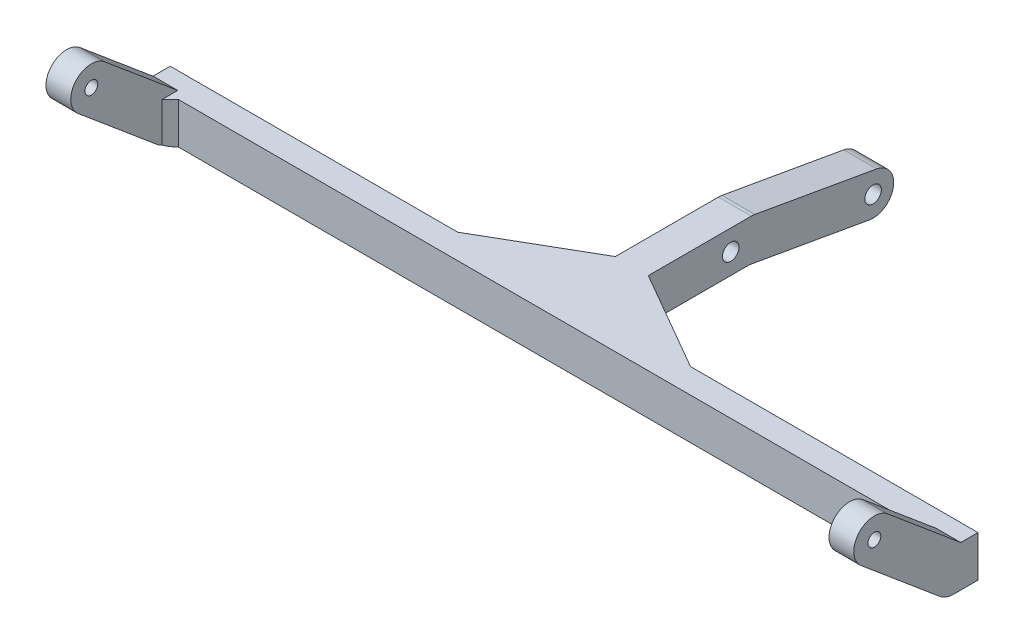
SolidWorks part; units mm, degrees
material "1060 合金"
ref_plane "前视基准面" through (0, 0, 0) normal (0, 0, 1) x (1, 0, 0)
ref_plane "上视基准面" through (0, 0, 0) normal (0, 1, 0) x (1, 0, 0)
ref_plane "右视基准面" through (0, 0, 0) normal (1, 0, 0) x (0, 0, -1)
sketch "草图1" plane through (0, 0, 0) normal (0, 1, 0) x (1, 0, 0)
  line L0 (0, 105.6524) -> (0, -42.1429) construction
  line L1 (98, 0) -> (-98, 0)
  line L7 (-24.7846, 8) -> (-4, 20)
  line L10 (-98, 8) -> (-24.7846, 8)
  line L20 (4, 50) -> (-4, 50)
  line L24 (-4, 20) -> (-4, 50)
  line L25 (-98, 0) -> (-98, 8)
  line L28 (98, 0) -> (98, 8)
  line L29 (4, 20) -> (4, 50)
  line L32 (98, 8) -> (24.7846, 8)
  line L33 (24.7846, 8) -> (4, 20)
  point P17 (0, -11.5)
  point P18 (0, 11.5)
  point P19 (0, 17.5)
  point P24 (0, -25)
  point P34 (0, 50)
  point P37 (0, 0)
  dimension "D1" = 8
  dimension "D2" = 4
  dimension "D3" = 30
  dimension "D4" = 50
  dimension "D7" = 12
  dimension "D9" = 98
extrude "凸台-拉伸1" add sketch "草图1" along normal mid plane 10
fillet "圆角1" radius 5 2 edges at (0, -5, -50) (0, 5, -50)
sketch "草图9" plane through (0, 0, 0) normal (1, 0, 0) x (0, 0, -1)
  line L0 (3.2139, 3.8302) -> (-15.9372, 19.8999)
  line L1 (-3.2139, -3.8302) -> (-22.365, 12.2395)
  line L2 (0, -5) -> (8, -5) construction
  arc A0 (-3.2139, -3.8302) -> (3.2139, 3.8302) centre (0, 0) ccw
  arc A1 (-15.9372, 19.8999) -> (-22.365, 12.2395) centre (-19.1511, 16.0697) ccw
  circle A2 centre (-19.1511, 16.0697) radius 1.5636
  dimension "D1" = 40
  dimension "D2" = 25
extrude "凸台-拉伸4" add sketch "草图9" against normal blind 6 from surface starting at face at (98, 0, -4)
extrude "凸台-拉伸5" add sketch "草图9<2>" along normal blind 6 from surface starting at face at (-98, 0, -4)
sketch "草图9<2>" plane through (0, 0, 0) normal (1, 0, 0) x (0, 0, -1) same geometry as "草图9"
sketch "草图10" plane through (0, 0, 0) normal (1, 0, 0) x (0, 0, -1)
  line L0 (45.8682, 4.924) -> (75.4125, -0.2854)
  line L1 (44.1318, -4.924) -> (73.676, -10.1335)
  line L2 (20, -5) -> (45, -5) construction
  arc A0 (45.8682, 4.924) -> (44.1318, -4.924) centre (45, 0) ccw
  arc A1 (73.676, -10.1335) -> (75.4125, -0.2854) centre (74.5442, -5.2094) ccw
  circle A2 centre (74.5442, -5.2094) radius 2
  arc A3 (45, -5) -> (50, 0) centre (45, 0) ccw construction
  dimension "D3" = 4
  dimension "D1" = 10
  dimension "D2" = 30
extrude "凸台-拉伸6" add sketch "草图10" along normal mid plane 8
sketch "草图11" plane through (0, 0, 0) normal (1, 0, 0) x (0, 0, -1)
  circle A0 centre (40, 0) radius 2
  dimension "D1" = 4
  dimension "D2" = 40
extrude "切除-拉伸1" cut sketch "草图11" against normal through all both and the other way through all
chamfer "倒角1" distance 2 angle 45 8 edges at (-92, 0, 0) (92, 0, 0) (-61.3923, -5, -8) (-98, 0, -8) (-61.3923, 5, -8) (61.3923, -5, -8) (98, 0, -8) (61.3923, 5, -8)
